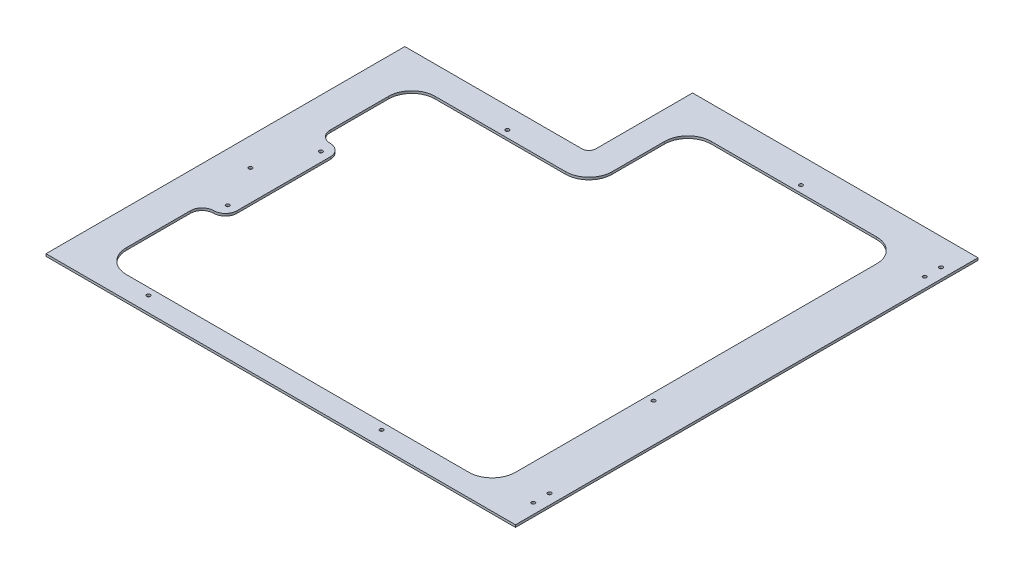
SolidWorks part; units mm, degrees
ref_plane "Alzado" through (0, 0, 0) normal (0, 0, 1) x (1, 0, 0)
ref_plane "Planta" through (0, 0, 0) normal (0, 1, 0) x (1, 0, 0)
ref_plane "Vista lateral" through (0, 0, 0) normal (1, 0, 0) x (0, 0, -1)
sketch "Croquis1" plane through (0, 0, 0) normal (0, 1, 0) x (1, 0, 0)
  line L1 (0, 0) -> (404, 0)
  line L2 (0, 0) -> (0, 400)
  line L3 (0, 400) -> (404, 400)
  line L4 (404, 0) -> (404, 400)
  dimension "D1" = 400
  dimension "D2" = 404
extrude "Saliente-Extruir1" add sketch "Croquis1" along normal blind 2
sketch "Croquis3" plane through (0, 0, 0) normal (0, -1, 0) x (1, 0, 0)
  line L1 (0, -400) -> (157, -400)
  line L2 (0, -400) -> (0, -310)
  line L3 (0, -310) -> (157, -310)
  line L4 (157, -400) -> (157, -310)
  dimension "D1" = 90
  dimension "157" = 157
extrude "Cortar-Extruir2" cut sketch "Croquis3" against normal up to surface (2 mm away) up to face at (202, 2, -200)
fillet "Redondeo1" radius 5 1 edges at (157, 1, -310)
sketch "Croquis4" plane through (0, 0, 0) normal (0, -1, 0) x (1, 0, 0)
  line L0 (404, 0) -> (404, -400) construction
  line L1 (30, -20) -> (364, -20)
  line L2 (30, -20) -> (30, -285)
  line L3 (30, -285) -> (182, -285)
  line L4 (364, -20) -> (364, -233.6615)
  line L6 (182, -285) -> (182, -370)
  line L7 (182, -370) -> (364, -370)
  line L8 (364, -233.6615) -> (364, -370)
  line L9 (404, -400) -> (157, -400) construction
  line L10 (0, 0) -> (404, 0) construction
  line L11 (0, -310) -> (0, 0) construction
  line L12 (152, -310) -> (0, -310) construction
  line L13 (157, -400) -> (157, -315) construction
  dimension "D1" = 40
  dimension "D2" = 30
  dimension "D3" = 20
  dimension "D4" = 30
  dimension "D5" = 25
  dimension "D6" = 25
extrude "Cortar-Extruir3" cut sketch "Croquis4" against normal up to surface (2 mm away) up to face at (182.1479, 2, -247.7092)
fillet "Redondeo2" radius 20 6 edges at (30, 1, -285) (182, 1, -285) (182, 1, -370) (364, 1, -370) (364, 1, -20) (30, 1, -20)
sketch "Croquis6" plane through (0, 0, 0) normal (0, -1, 0) x (1, 0, 0)
  line L0 (344, -20) -> (50, -20) construction
  line L1 (0, -310) -> (0, 0) construction
  line L2 (273, -370) -> (273, -243.2159) construction
  line L3 (202, -370) -> (344, -370) construction
  line L4 (50, -285) -> (162, -285) construction
  line L5 (30, -152.5) -> (364, -152.5) construction
  line L6 (30, -40) -> (30, -265) construction
  line L7 (364, -350) -> (364, -40) construction
  line L8 (106, -285) -> (106, -310) construction
  line L10 (152, -310) -> (0, -310) construction
  circle A0 centre (75, -14) radius 1.55
  circle A1 centre (275, -14) radius 1.55
  circle A2 centre (273, -376) radius 1.55
  circle A5 centre (106, -291) radius 1.55
  circle A6 centre (24, -152.5) radius 1.55
  circle A7 centre (370, -152.5) radius 1.55
  point P21 (106, -291)
  point P32 (106, -285)
  dimension "D1" = 3.1
  dimension "D5" = 3.1
  dimension "D2" = 6
  dimension "D3" = 200
  dimension "D4" = 75
  dimension "D6" = 6
  dimension "D7" = 6
  dimension "D8" = 6
  dimension "D9" = 6
extrude "Cortar-Extruir5" cut sketch "Croquis6" against normal up to surface (2 mm away) up to face at (192, 2, -225)
sketch "Croquis7" plane through (0, 0, 0) normal (0, -1, 0) x (1, 0, 0)
  line L0 (0, 0) -> (404, 0) construction
  line L2 (404, 0) -> (404, -400) construction
  line L3 (404, -400) -> (157, -400) construction
  line L4 (404, -200) -> (364, -200) construction
  line L5 (364, -350) -> (364, -40) construction
  circle A0 centre (394.25, -25) radius 1.55
  circle A1 centre (394.25, -39) radius 1.55
  circle A2 centre (394.25, -375) radius 1.55
  circle A3 centre (394.25, -361) radius 1.55
  dimension "D1" = 3.1
  dimension "D2" = 14
  dimension "D3" = 25
  dimension "D4" = 9.75
  dimension "D5" = 14
  dimension "D6" = 9.75
  dimension "D7" = 25
extrude "Cortar-Extruir6" cut sketch "Croquis7" against normal up to surface (2 mm away) up to face at (370, 2, -154.05)
sketch "Croquis8" plane through (0, 0, 0) normal (0, -1, 0) x (1, 0, 0)
  line L0 (0, -155) -> (136.8226, -155) construction
  line L1 (0, -310) -> (0, 0) construction
  line L2 (30, -40) -> (30, -265) construction
  line L3 (30, -105) -> (50, -105)
  line L4 (30, -105) -> (30, -205)
  line L5 (30, -205) -> (50, -205)
  line L6 (50, -105) -> (50, -205)
  dimension "D1" = 100
  dimension "D2" = 50
  dimension "D3" = 20
extrude "Saliente-Extruir2" add sketch "Croquis8" against normal up to surface (2 mm away) up to face at (394.25, 2, -26.55)
fillet "Redondeo3" radius 10 4 edges at (30, 1, -205) (50, 1, -205) (50, 1, -105) (30, 1, -105)
sketch "Croquis9" plane through (0, 0, 0) normal (0, -1, 0) x (1, 0, 0)
  line L0 (0, -155) -> (50, -155) construction
  line L1 (0, -310) -> (0, 0) construction
  line L2 (50, -195) -> (50, -115) construction
  circle A0 centre (42, -115) radius 1.55
  circle A1 centre (42, -195) radius 1.55
  dimension "D2" = 3.1
  dimension "D1" = 40
  dimension "D3" = 40
  dimension "D4" = 8
  dimension "D5" = 8
extrude "Cortar-Extruir7" cut sketch "Croquis9" against normal up to surface (2 mm away) up to face at (394.25, 2, -26.55)
sketch "Croquis10" plane through (0, 0, 0) normal (0, -1, 0) x (1, 0, 0)
  line L12 (1, -309) -> (152, -309)
  line L13 (158, -315) -> (158, -399)
  line L14 (158, -399) -> (403, -399)
  line L15 (403, -399) -> (403, -1)
  line L16 (403, -1) -> (1, -1)
  line L17 (1, -1) -> (1, -309)
  line L18 (1, -309) -> (152, -309)
  line L19 (158, -315) -> (158, -399)
  line L20 (158, -399) -> (403, -399)
  line L21 (403, -399) -> (403, -1)
  line L22 (403, -1) -> (1, -1)
  line L23 (1, -1) -> (1, -309)
  arc A2 (158, -315) -> (152, -309) centre (152, -315) ccw
  arc A3 (158, -315) -> (152, -309) centre (152, -315) ccw
  dimension "D1" = 1
extrude "Cortar-Extruir8" cut sketch "Croquis10" against normal blind 10 flip side to cut
sketch "Croquis11" plane through (0, 0, 0) normal (0, -1, 0) x (1, 0, 0)
  line L0 (403, -399) -> (403, -1) construction
  line L1 (158, -399) -> (403, -399)
  line L2 (158, -399) -> (158, -398)
  line L3 (158, -398) -> (403, -398)
  line L4 (403, -399) -> (403, -398)
  dimension "D1" = 1
extrude "Cortar-Extruir9" cut sketch "Croquis11" against normal up to surface (2 mm away) up to face at (141.3333, 2, -201.6667)
sketch "Croquis12" plane through (0, 0, 0) normal (0, -1, 0) x (1, 0, 0)
  line L1 (1, -1) -> (0, -1)
  line L2 (1, -1) -> (1, -309)
  line L3 (1, -309) -> (0, -309)
  line L4 (0, -1) -> (0, -309)
  dimension "D1" = 1
extrude "Saliente-Extruir3" add sketch "Croquis12" against normal up to surface (2 mm away) up to face at (141.3333, 2, -201.6667)
sketch "Croquis13" plane through (0, 0, 0) normal (0, -1, 0) x (1, 0, 0)
  line L0 (364, -350) -> (364, -40) construction
  line L1 (202, -370) -> (344, -370) construction
  line L2 (182, -305) -> (182, -350) construction
  line L3 (50, -285) -> (162, -285) construction
  line L4 (30, -215) -> (30, -265) construction
  line L5 (50, -195) -> (50, -115) construction
  line L6 (30, -40) -> (30, -95) construction
  line L7 (344, -20) -> (50, -20) construction
  line L8 (364, -350) -> (364, -40) construction
  line L9 (202, -370) -> (344, -370) construction
  line L10 (182, -305) -> (182, -350) construction
  line L11 (50, -285) -> (162, -285) construction
  line L12 (30, -215) -> (30, -265) construction
  line L13 (50, -195) -> (50, -115) construction
  line L14 (30, -40) -> (30, -95) construction
  line L15 (344, -20) -> (50, -20) construction
  line L16 (344, -5) -> (50, -5)
  line L17 (15, -40) -> (15, -95)
  line L19 (15, -215) -> (15, -265)
  line L20 (50, -300) -> (162, -300)
  line L21 (167, -305) -> (167, -350)
  line L22 (202, -385) -> (344, -385)
  line L23 (379, -350) -> (379, -40)
  line L24 (15, -95) -> (15, -215)
  line L26 (35, -190.5051) -> (35, -119.4949) construction
  arc A0 (364, -40) -> (344, -20) centre (344, -40) ccw construction
  arc A1 (344, -370) -> (364, -350) centre (344, -350) ccw construction
  arc A2 (182, -350) -> (202, -370) centre (202, -350) ccw construction
  arc A3 (182, -305) -> (162, -285) centre (162, -305) ccw construction
  arc A4 (30, -265) -> (50, -285) centre (50, -265) ccw construction
  arc A5 (40, -205) -> (30, -215) centre (40, -215) ccw construction
  arc A6 (40, -205) -> (50, -195) centre (40, -195) ccw construction
  arc A7 (50, -115) -> (40, -105) centre (40, -115) ccw construction
  arc A8 (30, -95) -> (40, -105) centre (40, -95) ccw construction
  arc A9 (50, -20) -> (30, -40) centre (50, -40) ccw construction
  arc A10 (364, -40) -> (344, -20) centre (344, -40) ccw construction
  arc A11 (344, -370) -> (364, -350) centre (344, -350) ccw construction
  arc A12 (182, -350) -> (202, -370) centre (202, -350) ccw construction
  arc A13 (182, -305) -> (162, -285) centre (162, -305) ccw construction
  arc A14 (30, -265) -> (50, -285) centre (50, -265) ccw construction
  arc A15 (40, -205) -> (30, -215) centre (40, -215) ccw construction
  arc A16 (40, -205) -> (50, -195) centre (40, -195) ccw construction
  arc A17 (50, -115) -> (40, -105) centre (40, -115) ccw construction
  arc A18 (30, -95) -> (40, -105) centre (40, -95) ccw construction
  arc A19 (50, -20) -> (30, -40) centre (50, -40) ccw construction
  arc A20 (50, -5) -> (15, -40) centre (50, -40) ccw
  circle A21 centre (75, -14) radius 2.25
  arc A22 (35, -119.4949) -> (35, -119.4949) centre (35, -119.4949) ccw
  arc A23 (35, -190.5051) -> (35, -190.5051) centre (35, -190.5051) ccw
  arc A25 (15, -265) -> (50, -300) centre (50, -265) ccw
  arc A26 (167, -305) -> (162, -300) centre (162, -305) ccw
  arc A27 (167, -350) -> (202, -385) centre (202, -350) ccw
  arc A28 (344, -385) -> (379, -350) centre (344, -350) ccw
  arc A29 (379, -40) -> (367.2438, -13.8327) centre (344, -40) ccw
  arc A30 (15, -95) -> (35, -119.4949) centre (40, -95) ccw construction
  arc A31 (35, -190.5051) -> (15, -215) centre (40, -215) ccw construction
  circle A32 centre (24, -152.5) radius 2.25
  circle A33 centre (42, -115) radius 5
  circle A34 centre (42, -195) radius 5
  circle A35 centre (106, -291) radius 2.25
  circle A36 centre (273, -376) radius 2.25
  circle A37 centre (370, -152.5) radius 2.25
  arc A38 (367.2438, -13.8327) -> (344, -5) centre (344, -40) ccw
  arc A39 (379, -40) -> (344, -5) centre (344, -40) ccw construction
  circle A40 centre (275, -14) radius 1.55 construction
  circle A41 centre (275, -14) radius 1.55 construction
  circle A42 centre (275, -14) radius 2.25
  dimension "D2" = 4.5
  dimension "D3" = 10
  dimension "D4" = 10
  dimension "D5" = 4.5
  dimension "D6" = 4.5
  dimension "D1" = 15
